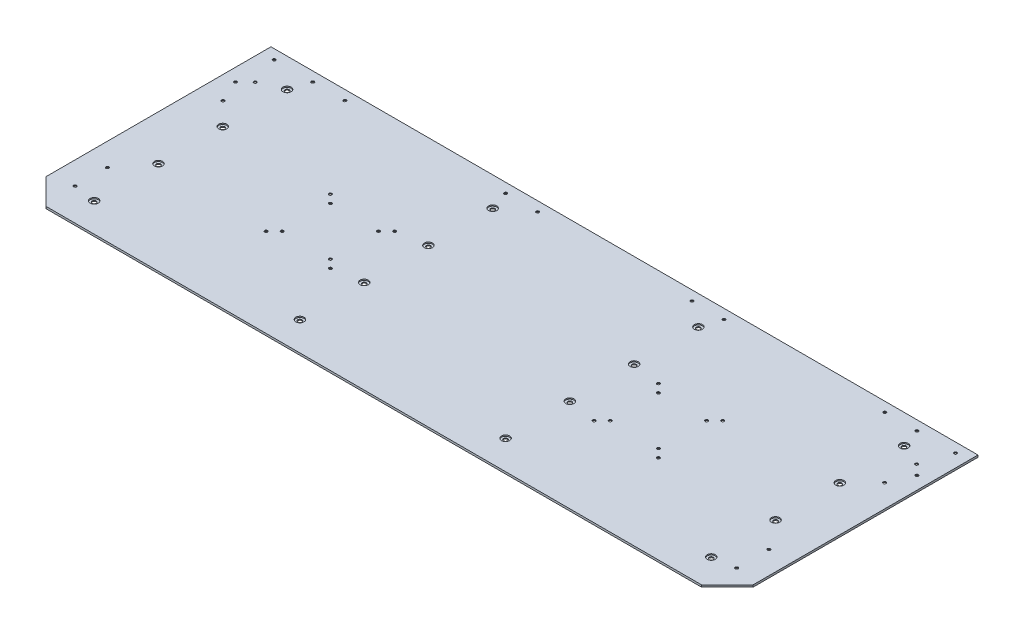
SolidWorks part; units mm, degrees
ref_plane "Front Plane" through (0, 0, 0) normal (0, 0, 1) x (1, 0, 0)
ref_plane "Top Plane" through (0, 0, 0) normal (0, 1, 0) x (1, 0, 0)
ref_plane "Right Plane" through (0, 0, 0) normal (1, 0, 0) x (0, 0, -1)
sketch "Sketch1" plane through (0, 0, 0) normal (0, 1, 0) x (1, 0, 0)
  line L1 (-550, -195) -> (550, -195)
  line L2 (-550, -195) -> (-550, 195)
  line L3 (-550, 195) -> (550, 195)
  line L4 (550, -195) -> (550, 195)
  line L5 (-550, -195) -> (550, 195) construction
  line L6 (-550, 195) -> (550, -195) construction
  point P0 (0, 0)
  dimension "D1" = 1100
  dimension "D2" = 390
extrude "Plate" add sketch "Sketch1" along normal blind 3.175
hole_wizard "Monitor Holes" positions "Sketch6" profile "Sketch7" countersink size "M4" standard "ANSI Metric" end condition through all
sketch "Sketch6" plane through (0, 0, 0) normal (0, -1, 0) x (-1, 0, 0)
  line L9 (-292.7, -44.9) -> (-217.7, -44.9)
  line L10 (-292.7, -44.9) -> (-292.7, 30.1)
  line L11 (-292.7, 30.1) -> (-217.7, 30.1)
  line L12 (-217.7, -44.9) -> (-217.7, 30.1)
  line L13 (-292.7, -44.9) -> (-217.7, 30.1) construction
  line L14 (-292.7, 30.1) -> (-217.7, -44.9) construction
  line L16 (-305.2, -57.4) -> (-205.2, -57.4)
  line L17 (-305.2, -57.4) -> (-305.2, 42.6)
  line L18 (-305.2, 42.6) -> (-205.2, 42.6)
  line L19 (-205.2, -57.4) -> (-205.2, 42.6)
  line L20 (-305.2, -57.4) -> (-205.2, 42.6) construction
  line L21 (-305.2, 42.6) -> (-205.2, -57.4) construction
  line L22 (0, 1.7463) -> (0, -1.7463) construction
  line L23 (292.7, 30.1) -> (217.7, 30.1)
  line L24 (292.7, -44.9) -> (217.7, -44.9)
  line L25 (292.7, -44.9) -> (292.7, 30.1)
  line L26 (305.2, -57.4) -> (205.2, -57.4)
  line L27 (305.2, -57.4) -> (305.2, 42.6)
  line L28 (217.7, -44.9) -> (217.7, 30.1)
  line L29 (205.2, -57.4) -> (205.2, 42.6)
  line L30 (305.2, 42.6) -> (205.2, 42.6)
  line L32 (-509.2, -159.8) -> (-1.2, -159.8)
  line L33 (-509.2, -159.8) -> (-509.2, 145)
  line L34 (-509.2, 145) -> (-1.2, 145)
  line L35 (-1.2, -159.8) -> (-1.2, 145)
  line L36 (-509.2, -159.8) -> (-1.2, 145) construction
  line L37 (-509.2, 145) -> (-1.2, -159.8) construction
  line L38 (-550, 175) -> (550, 175)
  line L39 (-550, -195) -> (-550, 195) construction
  line L40 (550, 195) -> (550, -195) construction
  line L42 (-550, 195) -> (550, 195) construction
  line L43 (0, 175) -> (0, -195)
  line L44 (550, -195) -> (-550, -195) construction
  point P80 (-217.7, 30.1)
  point P157 (-292.7, -44.9)
  point P158 (-292.7, 30.1)
  point P159 (-217.7, -44.9)
  point P161 (-205.2, 42.6)
  point P180 (-305.2, -57.4)
  point P181 (-305.2, 42.6)
  point P182 (-205.2, -57.4)
  point P186 (292.7, 30.1)
  point P187 (217.7, 30.1)
  point P188 (292.7, -44.9)
  point P189 (217.7, -44.9)
  point P190 (305.2, -57.4)
  point P191 (205.2, -57.4)
  point P192 (305.2, 42.6)
  point P193 (205.2, 42.6)
  point P307 (-255.2, -7.4)
  point P310 (-255.2, -7.4)
  point P311 (-255.2, -7.4)
  dimension "D1" = 508
  dimension "D2" = 304.8
  dimension "D3" = 20
  dimension "D4" = 75
  dimension "D5" = 100
  dimension "D6" = 40.8
  dimension "D7" = 30
sketch "Sketch7" plane through (217.7, 0, -30.1) normal (1, 0, 0) x (0, 0, -1)
  line L0 (0, 0) -> (0, 3.175)
  line L1 (0, 3.175) -> (2.25, 3.175)
  line L2 (2.25, 3.175) -> (2.25, 2.23)
  line L3 (2.25, 2.23) -> (4.48, 0)
  line L5 (4.48, 0) -> (0, 0)
  line L6 (-2.25, 2.23) -> (-4.48, 0) construction
  line L11 (0, -6.35) -> (0, 107.95) construction
  dimension "Thru Hole Dia." = 4.5
  dimension "Thru Hole Depth" = 3.175
  dimension "Near C'Sink Dia." = 8.96
  dimension "Near C'Sink Angle" = 90
hole_wizard "Strut Holes" positions "Sketch10" profile "Sketch12" hole size "M4" standard "ANSI Metric" end condition through all
sketch "Sketch10" plane through (0, 3.175, 0) normal (0, 1, 0) x (1, 0, 0)
  line L0 (-530, 180) -> (-530, 120)
  line L3 (-550, 195) -> (-550, -195) construction
  line L4 (0, -1.7463) -> (0, 1.7463) construction
  line L5 (530, 180) -> (530, 120)
  line L6 (550, 195) -> (-550, 195) construction
  point P1 (-530, 180)
  point P2 (-530, 120)
  point P11 (530, 180)
  point P12 (530, 120)
  point P13 (-530, 150)
  dimension "D1" = 60
  dimension "D2" = 45
  dimension "D3" = 20
sketch "Sketch12" plane through (-530, 3.175, -180) normal (1, 0, 0) x (0, 0, 1)
  line L0 (0, 0) -> (0, 3.175)
  line L1 (0, 3.175) -> (4.48, 3.175)
  line L2 (2.25, 0.945) -> (2.25, 0)
  line L5 (2.25, 0) -> (0, 0)
  line L7 (4.48, 3.175) -> (2.25, 0.945)
  line L8 (-4.48, 3.175) -> (-2.25, 0.945) construction
  line L11 (0, -6.35) -> (0, 107.95) construction
  dimension "Thru Hole Dia." = 4.5
  dimension "Thru Hole Depth" = 3.175
  dimension "Far C'Sink Dia." = 8.96
  dimension "Far C'Sink Angle" = 90
hole_wizard "Glare Protector Holes" positions "Sketch15" profile "Sketch16" hole size "M4" standard "ANSI Metric" end condition through all
sketch "Sketch15" plane through (0, 3.175, 0) normal (0, 1, 0) x (1, 0, 0)
  line L0 (-514.6, 135) -> (-514.6, 85)
  line L2 (-514.6, -145) -> (-514.6, -95)
  line L6 (550, 195) -> (-550, 195) construction
  line L8 (-470, 180) -> (-420, 180)
  line L10 (-170, 180) -> (-120, 180)
  line L12 (420, 180) -> (470, 180)
  line L14 (120, 180) -> (170, 180)
  line L16 (-550, 195) -> (-550, -195) construction
  line L17 (550, -195) -> (550, 195) construction
  line L18 (0, -1.7463) -> (0, 1.7463) construction
  line L19 (514.6, 135) -> (514.6, 85)
  line L21 (514.6, -145) -> (514.6, -95)
  line L22 (-550, -195) -> (550, -195) construction
  point P1 (-514.6, 135)
  point P2 (-514.6, 85)
  point P5 (-514.6, -145)
  point P6 (-514.6, -95)
  point P19 (-470, 180)
  point P20 (-420, 180)
  point P23 (-170, 180)
  point P24 (-120, 180)
  point P26 (420, 180)
  point P27 (470, 180)
  point P30 (120, 180)
  point P31 (170, 180)
  point P40 (514.6, 135)
  point P41 (514.6, 85)
  point P44 (514.6, -145)
  point P45 (514.6, -95)
  dimension "D1" = 50
  dimension "D2" = 60
  dimension "D3" = 230
  dimension "D4" = 80
  dimension "D5" = 80
  dimension "D6" = 50
  dimension "D7" = 300
  dimension "D8" = 300
  dimension "D9" = 15
  dimension "D10" = 35.4
  dimension "D11" = 45
  dimension "D12" = 50
  dimension "D13" = 44.6
sketch "Sketch16" plane through (-514.6, 3.175, -135) normal (1, 0, 0) x (0, 0, 1)
  line L0 (0, 0) -> (0, 3.175)
  line L1 (0, 3.175) -> (4.48, 3.175)
  line L2 (2.25, 0.945) -> (2.25, 0)
  line L5 (2.25, 0) -> (0, 0)
  line L7 (4.48, 3.175) -> (2.25, 0.945)
  line L8 (-4.48, 3.175) -> (-2.25, 0.945) construction
  line L11 (0, -6.35) -> (0, 107.95) construction
  dimension "Thru Hole Dia." = 4.5
  dimension "Thru Hole Depth" = 3.175
  dimension "Far C'Sink Dia." = 8.96
  dimension "Far C'Sink Angle" = 90
chamfer "Chamfer1" distance 40 angle 45 2 edges at (550, 1.5875, 195) (-550, 1.5875, 195)
hole_wizard "Carriage Holes" positions "Sketch21" profile "Sketch23" counterbore size "M5" standard "ANSI Metric" end condition through all
sketch "Sketch21" plane through (0, 3.175, 0) normal (0, 1, 0) x (1, 0, 0)
  point P0 (160, -150)
  point P2 (480, -150)
  point P14 (160, -50)
  point P15 (480, -50)
  point P16 (160, 50)
  point P17 (480, 50)
  point P18 (160, 150)
  point P19 (480, 150)
  dimension "D1" = 160
  dimension "D2" = 150
  dimension "D3" = 480
  dimension "D4" = 4
sketch "Sketch23" plane through (160, 3.175, 150) normal (1, 0, 0) x (0, 0, 1)
  line L0 (0, 0) -> (0, 3.175)
  line L1 (0, 3.175) -> (3.175, 3.175)
  line L3 (3.175, 3.175) -> (3.175, 1.7875)
  line L4 (3.175, 1.7875) -> (6.35, 1.7875)
  line L5 (6.35, 1.7875) -> (6.35, 0)
  line L7 (6.35, 0) -> (0, 0)
  line L11 (0, -6.35) -> (0, 107.95) construction
  dimension "Thru Hole Dia." = 6.35
  dimension "Thru Hole Depth" = 3.175
  dimension "C'Bore Dia." = 12.7
  dimension "C'Bore Depth" = 1.7875
mirror "Mirror1" about plane through (0, 0, 0) normal (1, 0, 0) of "Carriage Holes"
